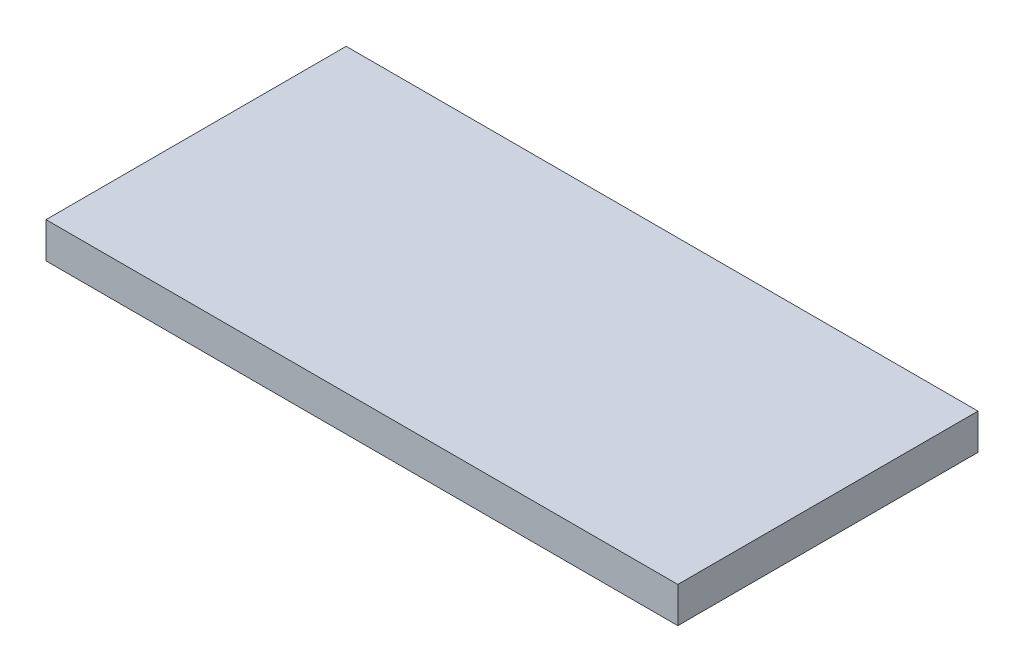
SolidWorks part; units mm, degrees
ref_plane "Front Plane" through (0, 0, 0) normal (0, 0, 1) x (1, 0, 0)
ref_plane "Top Plane" through (0, 0, 0) normal (0, 1, 0) x (1, 0, 0)
ref_plane "Right Plane" through (0, 0, 0) normal (1, 0, 0) x (0, 0, -1)
sketch "Sketch2" plane through (0, 0, 0) normal (0, 1, 0) x (1, 0, 0)
  line L1 (-110.5, 52.5) -> (110.5, 52.5)
  line L2 (-110.5, 52.5) -> (-110.5, -52.5)
  line L3 (-110.5, -52.5) -> (110.5, -52.5)
  line L4 (110.5, 52.5) -> (110.5, -52.5)
  dimension "D1" = 221
  dimension "D2" = 105
  dimension "D3" = 110.5
  dimension "D4" = 52.5
extrude "Boss-Extrude1" add sketch "Sketch2" along normal blind 2.5
sketch "Sketch3" plane through (0, 0, 0) normal (0, -1, 0) x (1, 0, 0)
  line L13 (110.5, -52.5) -> (-110.5, -52.5)
  line L14 (110.5, -52.5) -> (110.5, 52.5)
  line L15 (110.5, 52.5) -> (-110.5, 52.5)
  line L16 (-108, 50) -> (-108, -50)
  line L17 (108, 50) -> (-108, 50)
  line L18 (-108, -50) -> (108, -50)
  line L19 (108, -50) -> (108, 50)
  line L20 (-108, 50) -> (-108, -50)
  line L21 (108, 50) -> (-108, 50)
  line L22 (-108, -50) -> (108, -50)
  line L23 (108, -50) -> (108, 50)
  line L24 (-110.5, -52.5) -> (-110.5, 52.5)
  dimension "D1" = 2.5
extrude "Boss-Extrude2" add sketch "Sketch3" along normal blind 10
equation "\"D3@Sketch2\"=\"D1@Sketch2\"/2"
equation "\"D4@Sketch2\"=\"D2@Sketch2\"/2"
